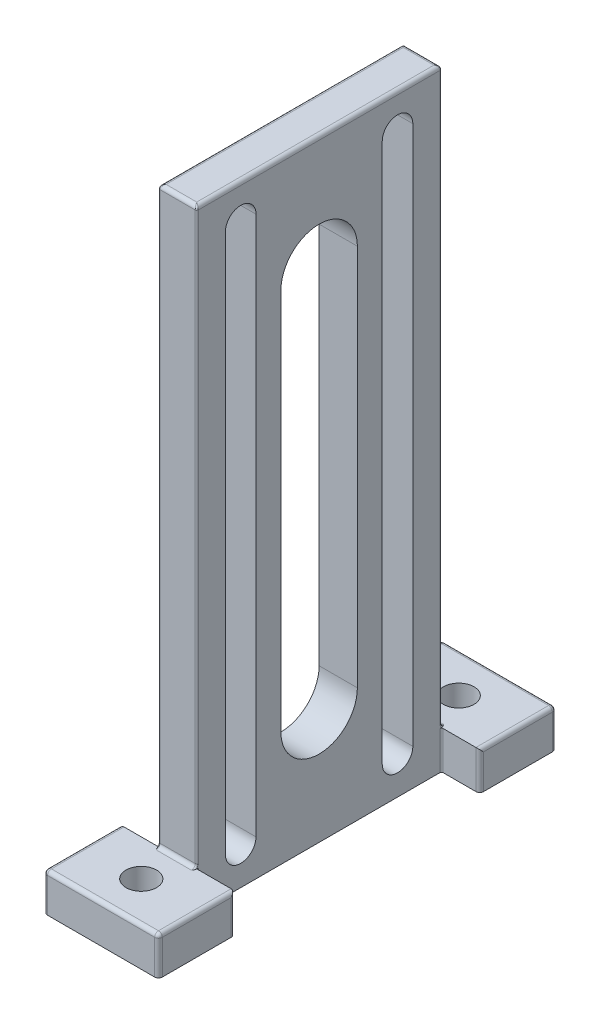
SolidWorks part; units mm, degrees
ref_plane "Front Plane" through (0, 0, 0) normal (0, 0, 1) x (1, 0, 0)
ref_plane "Top Plane" through (0, 0, 0) normal (0, 1, 0) x (1, 0, 0)
ref_plane "Right Plane" through (0, 0, 0) normal (1, 0, 0) x (0, 0, -1)
sketch "Sketch1" plane through (0, 0, 0) normal (0, 0, 1) x (1, 0, 0)
  line L1 (-16, -40) -> (16, -40)
  line L2 (-16, -40) -> (-16, 40)
  line L3 (-16, 40) -> (16, 40)
  line L4 (16, -40) -> (16, 40)
  line L5 (-16, -40) -> (16, 40) construction
  line L6 (-16, 40) -> (16, -40) construction
  point P0 (0, 0)
  dimension "D1" = 32
  dimension "D2" = 80
extrude "Boss-Extrude1" add sketch "Sketch1" along normal mid plane 5
sketch "Sketch2" plane through (0, 0, 2.5) normal (0, 0, 1) x (1, 0, 0)
  line L2 (-5, 25) -> (-5, -25)
  line L3 (5, 25) -> (5, -25)
  line L5 (-16, -40) -> (16, -40) construction
  line L6 (16, 40) -> (-16, 40) construction
  arc A0 (-5, -25) -> (5, -25) centre (0, -25) ccw
  arc A1 (5, 25) -> (-5, 25) centre (0, 25) ccw
  point P6 (0, -40)
  dimension "D2" = 10
  dimension "D1" = 15
  dimension "D3" = 15
extrude "Cut-Extrude1" cut sketch "Sketch2" against normal up to next
sketch "Sketch3" plane through (0, 0, 2.5) normal (0, 0, 1) x (1, 0, 0)
  line L0 (-16, -40) -> (16, -40) construction
  line L2 (55, 0) -> (-55, 0) construction
  line L3 (-12.25, 35.25) -> (-12.25, -35.25)
  line L4 (-8.25, -35.25) -> (-8.25, 35.25)
  arc A0 (-8.25, 35.25) -> (-12.25, 35.25) centre (-10.25, 35.25) ccw
  arc A2 (-8.25, -35.25) -> (-12.25, -35.25) centre (-10.25, -35.25) cw
  dimension "D3" = 4.75
  dimension "D1" = 10.25
  dimension "D2" = 4
extrude "Cut-Extrude2" cut sketch "Sketch3" against normal up to next
mirror "Mirror1" about plane through (0, 0, 0) normal (1, 0, 0) of "Cut-Extrude2"
ref_plane "Plane1" through (0, -40, 0) normal (0, -1, 0) x (-1, 0, 0)
sketch "Sketch4" plane through (0, -40, 0) normal (0, -1, 0) x (-1, 0, 0)
  line L0 (16, -2.5) -> (16, 2.5) construction
  line L1 (16, 7.5) -> (26, 7.5)
  line L2 (16, 7.5) -> (16, -7.5)
  line L3 (16, -7.5) -> (26, -7.5)
  line L4 (26, 7.5) -> (26, -7.5)
  line L6 (0, 55) -> (0, -55) construction
  line L7 (-26, 7.5) -> (-26, -7.5)
  line L8 (-16, -7.5) -> (-26, -7.5)
  line L9 (-16, 7.5) -> (-16, -7.5)
  line L10 (-16, 7.5) -> (-26, 7.5)
  point P6 (16, 0)
  point P7 (16, 0)
  dimension "D1" = 15
  dimension "D2" = 10
extrude "Boss-Extrude2" add sketch "Sketch4" against normal blind 5
fillet "Fillet1" radius 0.5 20 edges at (16, 40, 0) (0, 40, 2.5) (-16, 40, 0) (0, 40, -2.5) (-16, -37.5, 7.5) (16, -37.5, 7.5) (16, -37.5, -7.5) (-16, -37.5, -7.5) (-21, -35, 7.5) (-26, -37.5, 7.5) (-26, -35, 0) (-26, -37.5, -7.5) (-21, -35, -7.5) (21, -35, 7.5) (26, -37.5, 7.5) (26, -37.5, -7.5) (21, -35, -7.5) (26, -35, 0) (16, -35, 0) (-16, -35, 0)
fillet "Fillet2" radius 0.2 16 edges at (-15.8536, 39.8536, 2.3536) (-16.1464, -34.8536, 2.5) (-15.8536, 39.8536, -2.3536) (-16.1464, -34.8536, -2.5) (16.1464, -34.8536, -2.5) (15.8536, 39.8536, -2.3536) (16.1464, -34.8536, 2.5) (15.8536, 39.8536, 2.3536) (-16, 2.5, 2.5) (-16, 2.5, -2.5) (16, 2.5, -2.5) (16, 2.5, 2.5) (-16, -37.5, 2.5) (16, -37.5, 2.5) (-16, -37.5, -2.5) (16, -37.5, -2.5)
sketch "Sketch5" plane through (0, -35, 0) normal (0, 1, 0) x (1, 0, 0)
  line L0 (20.75, 7) -> (20.75, -7) construction
  line L1 (25.5, 7) -> (16, 7) construction
  line L2 (16, -7) -> (25.5, -7) construction
  circle A0 centre (20.75, 0) radius 2
  dimension "D1" = 4
extrude "Cut-Extrude3" cut sketch "Sketch5" against normal up to next
mirror "Mirror2" about plane through (0, 0, 0) normal (1, 0, 0) of "Cut-Extrude3"
move or copy body "Body-Move/Copy1" bodies to move or copy 107 copy no rotation origin (0, 0, 0) rotation axis (0, 1, 0) rotation angle 90
